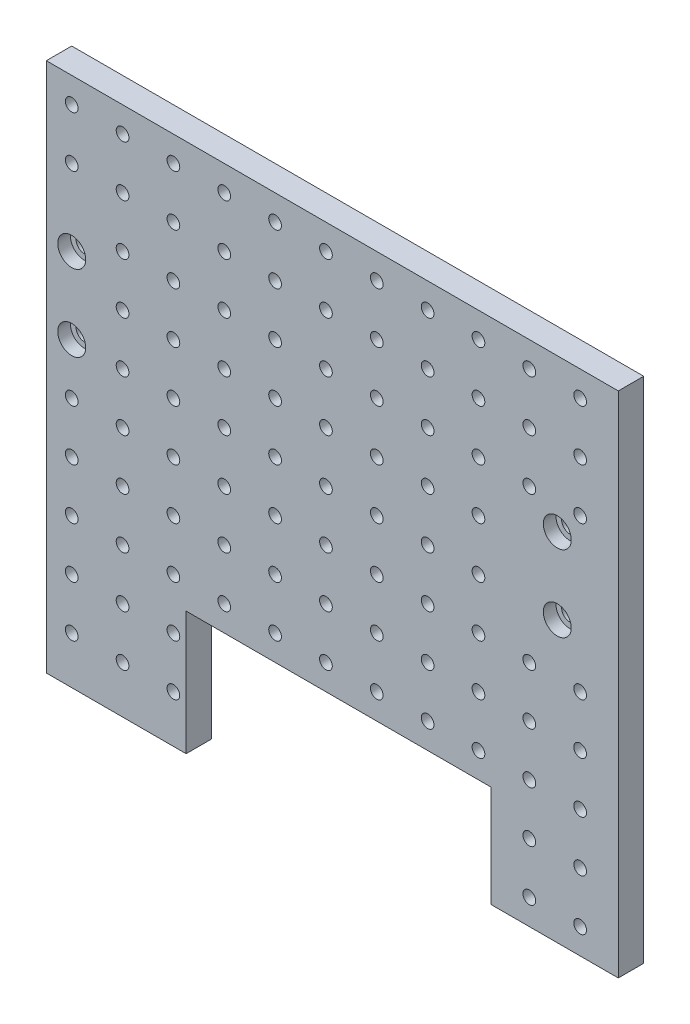
SolidWorks part; units mm, degrees
ref_plane "Front Plane" through (0, 0, 0) normal (0, 0, 1) x (1, 0, 0)
ref_plane "Top Plane" through (0, 0, 0) normal (0, 1, 0) x (1, 0, 0)
ref_plane "Right Plane" through (0, 0, 0) normal (1, 0, 0) x (0, 0, -1)
sketch "Sketch1" plane through (0, 0, 0) normal (0, 0, 1) x (1, 0, 0)
  line L1 (69.85, 0) -> (222.25, 0)
  line L2 (0, 0) -> (0, 203.2)
  line L3 (0, 203.2) -> (285.75, 203.2)
  line L4 (285.75, 0) -> (285.75, 203.2)
  line L6 (285.75, 0) -> (285.75, -50.8)
  line L7 (285.75, -50.8) -> (222.25, -50.8)
  line L8 (222.25, 0) -> (222.25, -50.8)
  line L10 (0, 0) -> (0, -61.722)
  line L11 (0, -61.722) -> (69.85, -61.722)
  line L12 (69.85, 0) -> (69.85, -61.722)
  circle A0 centre (12.7, 190.5) radius 3.175
  circle A1 centre (38.1, 190.5) radius 3.175
  circle A2 centre (63.5, 190.5) radius 3.175
  circle A3 centre (88.9, 190.5) radius 3.175
  circle A4 centre (114.3, 190.5) radius 3.175
  circle A5 centre (139.7, 190.5) radius 3.175
  circle A6 centre (165.1, 190.5) radius 3.175
  circle A7 centre (190.5, 190.5) radius 3.175
  circle A8 centre (215.9, 190.5) radius 3.175
  circle A9 centre (241.3, 190.5) radius 3.175
  circle A10 centre (266.7, 190.5) radius 3.175
  circle A11 centre (38.1, 165.1) radius 3.175
  circle A12 centre (63.5, 165.1) radius 3.175
  circle A13 centre (88.9, 165.1) radius 3.175
  circle A14 centre (114.3, 165.1) radius 3.175
  circle A15 centre (139.7, 165.1) radius 3.175
  circle A16 centre (165.1, 165.1) radius 3.175
  circle A17 centre (190.5, 165.1) radius 3.175
  circle A18 centre (215.9, 165.1) radius 3.175
  circle A19 centre (241.3, 165.1) radius 3.175
  circle A20 centre (266.7, 165.1) radius 3.175
  circle A21 centre (38.1, 139.7) radius 3.175
  circle A22 centre (63.5, 139.7) radius 3.175
  circle A23 centre (88.9, 139.7) radius 3.175
  circle A24 centre (114.3, 139.7) radius 3.175
  circle A25 centre (139.7, 139.7) radius 3.175
  circle A26 centre (165.1, 139.7) radius 3.175
  circle A27 centre (190.5, 139.7) radius 3.175
  circle A28 centre (215.9, 139.7) radius 3.175
  circle A29 centre (241.3, 139.7) radius 3.175
  circle A30 centre (266.7, 139.7) radius 3.175
  circle A31 centre (38.1, 114.3) radius 3.175
  circle A32 centre (63.5, 114.3) radius 3.175
  circle A33 centre (88.9, 114.3) radius 3.175
  circle A34 centre (114.3, 114.3) radius 3.175
  circle A35 centre (139.7, 114.3) radius 3.175
  circle A36 centre (165.1, 114.3) radius 3.175
  circle A37 centre (190.5, 114.3) radius 3.175
  circle A38 centre (215.9, 114.3) radius 3.175
  circle A41 centre (38.1, 88.9) radius 3.175
  circle A42 centre (63.5, 88.9) radius 3.175
  circle A43 centre (88.9, 88.9) radius 3.175
  circle A44 centre (114.3, 88.9) radius 3.175
  circle A45 centre (139.7, 88.9) radius 3.175
  circle A46 centre (165.1, 88.9) radius 3.175
  circle A47 centre (190.5, 88.9) radius 3.175
  circle A48 centre (215.9, 88.9) radius 3.175
  circle A51 centre (38.1, 63.5) radius 3.175
  circle A52 centre (63.5, 63.5) radius 3.175
  circle A53 centre (88.9, 63.5) radius 3.175
  circle A54 centre (114.3, 63.5) radius 3.175
  circle A55 centre (139.7, 63.5) radius 3.175
  circle A56 centre (165.1, 63.5) radius 3.175
  circle A57 centre (190.5, 63.5) radius 3.175
  circle A58 centre (215.9, 63.5) radius 3.175
  circle A59 centre (241.3, 63.5) radius 3.175
  circle A60 centre (266.7, 63.5) radius 3.175
  circle A61 centre (38.1, 38.1) radius 3.175
  circle A62 centre (63.5, 38.1) radius 3.175
  circle A63 centre (88.9, 38.1) radius 3.175
  circle A64 centre (114.3, 38.1) radius 3.175
  circle A65 centre (139.7, 38.1) radius 3.175
  circle A66 centre (165.1, 38.1) radius 3.175
  circle A67 centre (190.5, 38.1) radius 3.175
  circle A68 centre (215.9, 38.1) radius 3.175
  circle A69 centre (241.3, 38.1) radius 3.175
  circle A71 centre (38.1, 12.7) radius 3.175
  circle A72 centre (63.5, 12.7) radius 3.175
  circle A73 centre (88.9, 12.7) radius 3.175
  circle A74 centre (114.3, 12.7) radius 3.175
  circle A75 centre (139.7, 12.7) radius 3.175
  circle A76 centre (165.1, 12.7) radius 3.175
  circle A77 centre (190.5, 12.7) radius 3.175
  circle A78 centre (215.9, 12.7) radius 3.175
  circle A79 centre (241.3, 12.7) radius 3.175
  circle A81 centre (38.1, -12.7) radius 3.175
  circle A82 centre (63.5, -12.7) radius 3.175
  circle A89 centre (241.3, -12.7) radius 3.175
  circle A90 centre (266.7, -12.7) radius 3.175
  circle A91 centre (38.1, -38.1) radius 3.175
  circle A92 centre (63.5, -38.1) radius 3.175
  circle A99 centre (241.3, -38.1) radius 3.175
  circle A100 centre (266.7, -38.1) radius 3.175
  circle A101 centre (12.7, 165.1) radius 3.175
  circle A104 centre (12.7, 88.9) radius 3.175
  circle A105 centre (12.7, 63.5) radius 3.175
  circle A106 centre (12.7, 38.1) radius 3.175
  circle A107 centre (12.7, 12.7) radius 3.175
  circle A108 centre (12.7, -12.7) radius 3.175
  circle A109 centre (12.7, -38.1) radius 3.175
  circle A110 centre (88.9, -12.7) radius 3.175 [skipped]
  circle A111 centre (114.3, -12.7) radius 3.175 [skipped]
  circle A112 centre (139.7, -12.7) radius 3.175 [skipped]
  circle A113 centre (165.1, -12.7) radius 3.175 [skipped]
  circle A114 centre (190.5, -12.7) radius 3.175 [skipped]
  circle A115 centre (215.9, -12.7) radius 3.175 [skipped]
  circle A116 centre (215.9, -38.1) radius 3.175 [skipped]
  circle A117 centre (190.5, -38.1) radius 3.175 [skipped]
  circle A118 centre (165.1, -38.1) radius 3.175 [skipped]
  circle A119 centre (139.7, -38.1) radius 3.175 [skipped]
  circle A120 centre (114.3, -38.1) radius 3.175 [skipped]
  circle A121 centre (88.9, -38.1) radius 3.175 [skipped]
  circle A122 centre (266.7, 38.1) radius 3.175 [skipped]
  circle A123 centre (266.7, 12.7) radius 3.175 [skipped]
  circle A124 centre (12.7, 114.3) radius 3.175 [skipped]
  circle A125 centre (12.7, 139.7) radius 3.175 [skipped]
  circle A126 centre (266.7, 114.3) radius 3.175 [skipped]
  circle A127 centre (266.7, 88.9) radius 3.175 [skipped]
  circle A128 centre (241.3, 88.9) radius 3.175 [skipped]
  circle A129 centre (241.3, 114.3) radius 3.175 [skipped]
  circle A130 centre (266.7, 38.1) radius 3.175
  circle A131 centre (266.7, 12.7) radius 3.175
  dimension "D7" = 6.35
  dimension "D1" = 203.2
  dimension "D2" = 285.75
  dimension "D3" = 50.8
  dimension "D4" = 63.5
  dimension "D5" = 61.722
  dimension "D6" = 69.85
  dimension "D8" = 12.7
  dimension "D9" = 12.7
  dimension "D10" = 11
  dimension "D11" = 10
extrude "Boss-Extrude2" add sketch "Sketch1" along normal blind 12.7
sketch "Sketch3" plane through (0, 0, 12.7) normal (0, 0, 1) x (1, 0, 0)
  line L0 (285.75, 203.2) -> (0, 203.2) construction
  line L1 (0, 203.2) -> (0, -61.722) construction
  line L2 (285.75, -50.8) -> (285.75, 203.2) construction
  circle A0 centre (255.27, 127) radius 4.191
  circle A1 centre (255.27, 127) radius 6.985
  circle A2 centre (255.27, 88.9) radius 4.191
  circle A3 centre (255.27, 88.9) radius 6.985
  circle A4 centre (12.7, 127) radius 4.191
  circle A5 centre (12.7, 127) radius 6.985
  circle A6 centre (12.7, 88.9) radius 4.191
  circle A7 centre (12.7, 88.9) radius 6.985
  dimension "D1" = 8.382
  dimension "D2" = 13.97
  dimension "D3" = 38.1
  dimension "D4" = 38.1
  dimension "D5" = 76.2
  dimension "D6" = 76.2
  dimension "D7" = 12.7
  dimension "D8" = 30.48
extrude "Cut-Extrude1" cut sketch "Sketch3" along direction (0, 0, 1) on the side against the normal offset from surface (6.35 mm away) 6.35 contours A1 A0 | A3 A2 | A5 A4 | A7 A6 region at (248.4826, 127, 12.7) region at (248.4826, 88.9, 12.7) region at (5.9126, 127, 12.7) region at (5.9126, 88.9, 12.7) up to face at (15.875, -12.7, 12.7)
extrude "Cut-Extrude2" cut sketch "Sketch3<3>" along direction (0, 0, 1) on the side against the normal offset from surface (12.7 mm away) 12.7 contours A2 | A0 | A6 | A4 region at (255.27, 127, 12.7) region at (255.27, 88.9, 12.7) region at (12.7, 127, 12.7) region at (12.7, 88.9, 12.7) up to face at (259.461, 127, 12.7)
sketch "Sketch3<3>" plane through (0, 0, 12.7) normal (0, 0, 1) x (1, 0, 0) same geometry as "Sketch3"
